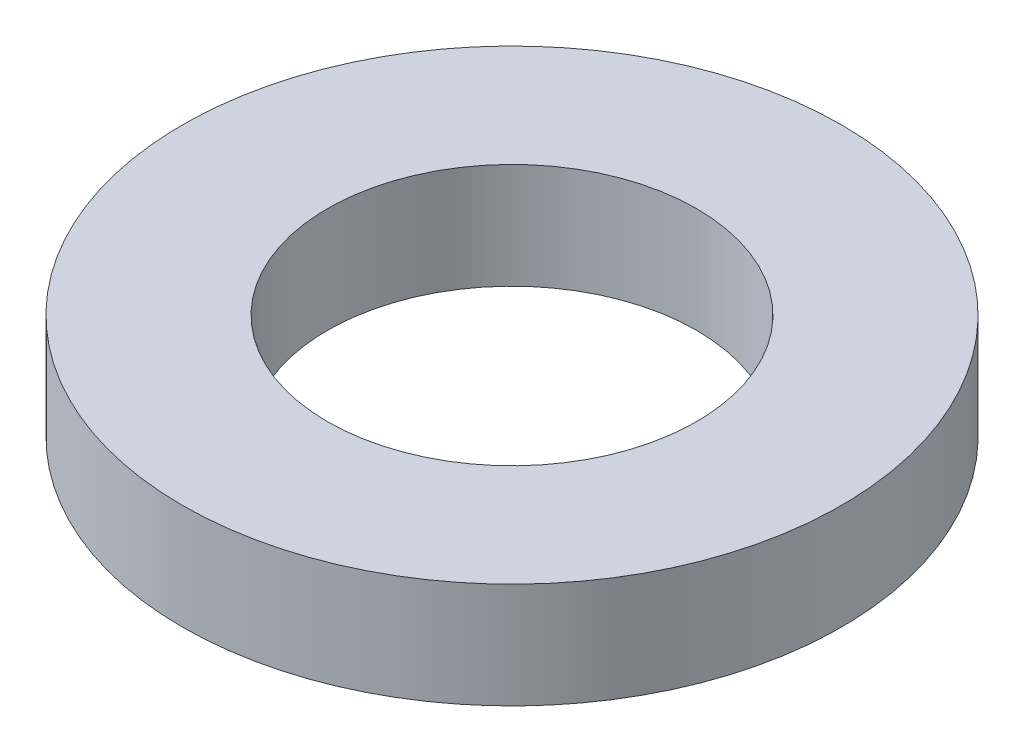
SolidWorks part; units mm, degrees
ref_plane "Front Plane" through (0, 0, 0) normal (0, 0, 1) x (1, 0, 0)
ref_plane "Top Plane" through (0, 0, 0) normal (0, 1, 0) x (1, 0, 0)
ref_plane "Right Plane" through (0, 0, 0) normal (1, 0, 0) x (0, 0, -1)
sketch "Sketch1" plane through (0, 0, 0) normal (0, 1, 0) x (1, 0, 0)
  circle A0 centre (0, 0) radius 62.5
  dimension "FLANGE_OD" = 125
extrude "Boss-Extrude1" add sketch "Sketch1" along normal blind 20
sketch "Sketch2" plane through (0, 0, 0) normal (0, 1, 0) x (1, 0, 0)
  circle A0 centre (0, 0) radius 35
  dimension "BORE_D" = 70
extrude "Cut-Extrude1" cut sketch "Sketch2" along normal through all
sketch "Sketch3" plane through (0, 20, 0) normal (0, 1, 0) x (1, 0, 0)
  circle A0 centre (0, 0) radius 25.6552 construction
  circle A1 centre (-25.6552, 0) radius 3.6373
  dimension "BOLT_D" = 7.2746
  dimension "BOLT_PCD" = 51.3103
extrude "Cut-Extrude2" cut sketch "Sketch3" against normal blind 17.5694 rebuild error yes
pattern_circular "CirPattern1" count 6 over 360 rebuild error yes
